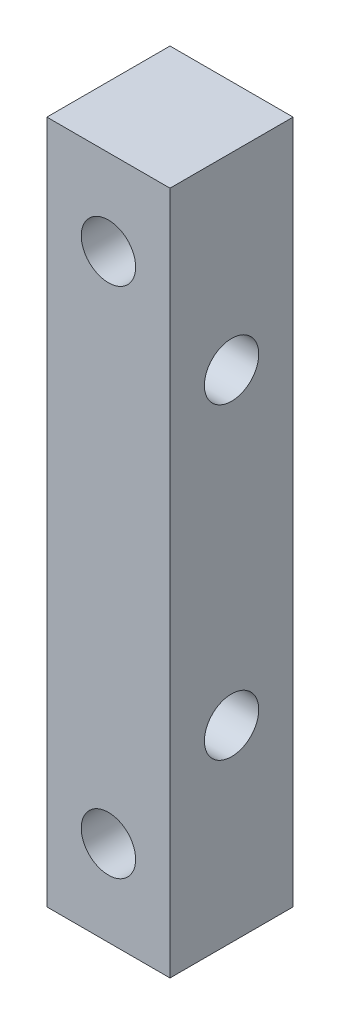
SolidWorks part; units mm, degrees
material "6061-T6 (SS)"
ref_plane "Front Plane" through (0, 0, 0) normal (0, 0, 1) x (1, 0, 0)
ref_plane "Top Plane" through (0, 0, 0) normal (0, 1, 0) x (1, 0, 0)
ref_plane "Right Plane" through (0, 0, 0) normal (1, 0, 0) x (0, 0, -1)
sketch "Sketch1" plane through (0, 0, 0) normal (0, 1, 0) x (1, 0, 0)
  line L1 (-4.572, 4.572) -> (4.572, 4.572)
  line L2 (-4.572, 4.572) -> (-4.572, -4.572)
  line L3 (-4.572, -4.572) -> (4.572, -4.572)
  line L4 (4.572, 4.572) -> (4.572, -4.572)
  line L5 (-4.572, 4.572) -> (4.572, -4.572) construction
  line L6 (-4.572, -4.572) -> (4.572, 4.572) construction
  point P0 (0, 0)
  dimension "D1" = 9.144
extrude "Boss-Extrude1" add sketch "Sketch1" along normal blind 50.8
sketch "Sketch3" plane through (0, 0, 4.572) normal (0, 0, 1) x (1, 0, 0)
  line L0 (0, 44.45) -> (0, 6.35) construction
  line L1 (4.572, 50.8) -> (4.572, 0) construction
  point P3 (0, 25.4)
  point P8 (4.572, 25.4)
  dimension "D1" = 38.1
hole_wizard "Tap Drill for #10-32 Tap1" positions "Sketch4" profile "Sketch6" hole size "#10-32" standard "ANSI Inch" end condition through all
sketch "Sketch4" plane through (0, 0, 4.572) normal (0, 0, 1) x (1, 0, 0)
  point P0 (0, 44.45)
  point P3 (0, 6.35)
sketch "Sketch6" plane through (0, 44.45, 4.572) normal (1, 0, 0) x (0, -1, 0)
  line L0 (0, 0) -> (0, 9.144)
  line L1 (0, 9.144) -> (2.0193, 9.144)
  line L2 (2.0193, 9.144) -> (2.0193, 0)
  line L5 (2.0193, 0) -> (0, 0)
  line L11 (0, -6.35) -> (0, 107.95) construction
  dimension "Thru Hole Dia." = 4.0386
  dimension "Thru Hole Depth" = 9.144
sketch "Sketch7" plane through (4.572, 0, 0) normal (1, 0, 0) x (0, 0, -1)
  line L0 (0, 36.83) -> (0, 13.97) construction
  line L1 (-4.572, 50.8) -> (-4.572, 0) construction
  line L2 (-4.572, 0) -> (4.572, 0) construction
  point P2 (-4.572, 25.4)
  point P3 (0, 25.4)
  point P8 (0, 0)
  dimension "D1" = 22.86
hole_wizard "Tap Drill for #10-32 Tap2" positions "Sketch10" profile "Sketch11" hole size "#10-32" standard "ANSI Inch" end condition through all
sketch "Sketch10" plane through (4.572, 0, 0) normal (1, 0, 0) x (0, 0, -1)
  point P0 (0, 36.83)
  point P3 (0, 13.97)
sketch "Sketch11" plane through (4.572, 36.83, 0) normal (0, 1, 0) x (0, 0, -1)
  line L0 (0, 0) -> (0, 9.144)
  line L1 (0, 9.144) -> (2.0193, 9.144)
  line L2 (2.0193, 9.144) -> (2.0193, 0)
  line L5 (2.0193, 0) -> (0, 0)
  line L11 (0, -6.35) -> (0, 107.95) construction
  dimension "Thru Hole Dia." = 4.0386
  dimension "Thru Hole Depth" = 9.144
